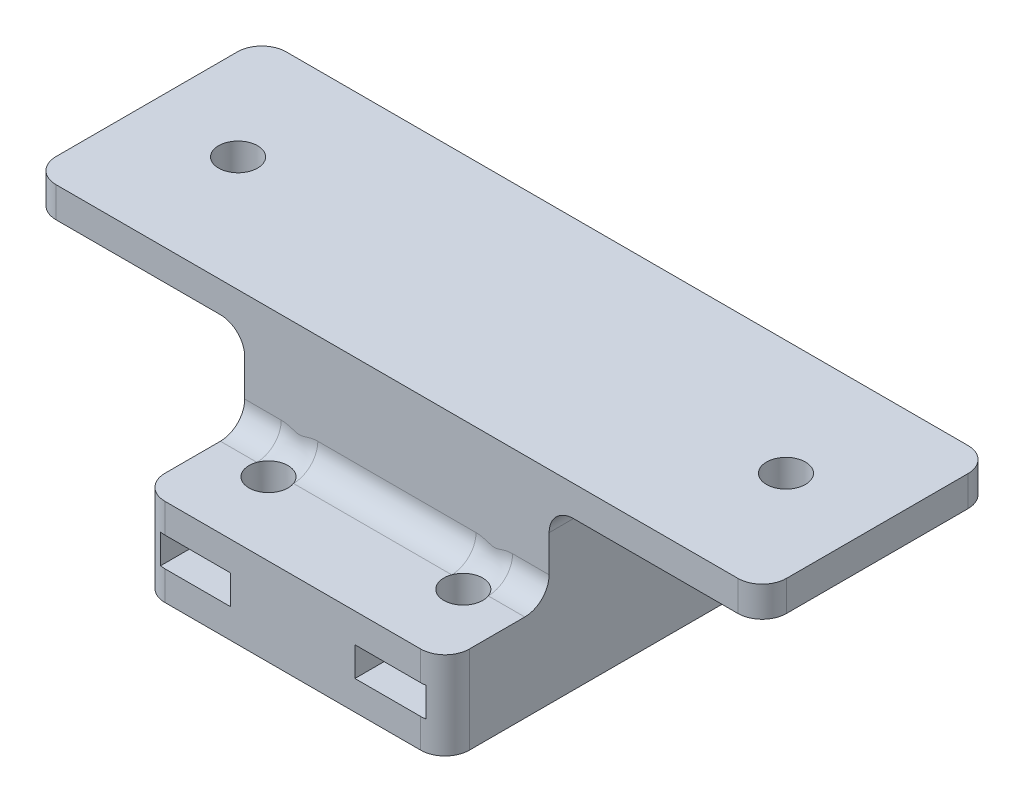
SolidWorks part; units mm, degrees
ref_plane "Front Plane" through (0, 0, 0) normal (0, 0, 1) x (1, 0, 0)
ref_plane "Top Plane" through (0, 0, 0) normal (0, 1, 0) x (1, 0, 0)
ref_plane "Right Plane" through (0, 0, 0) normal (1, 0, 0) x (0, 0, -1)
sketch "Sketch2" plane through (0, 0, 0) normal (0, 1, 0) x (1, 0, 0)
  line L1 (-12.5, 18) -> (12.5, 18)
  line L2 (-12.5, 18) -> (-12.5, -18)
  line L3 (-12.5, -18) -> (12.5, -18)
  line L4 (12.5, 18) -> (12.5, -18)
  line L5 (-12.5, 18) -> (12.5, -18) construction
  line L6 (-12.5, -18) -> (12.5, 18) construction
  point P0 (0, 0)
  dimension "D1" = 25
  dimension "D2" = 36
extrude "Boss-Extrude1" add sketch "Sketch2" along normal blind 7.2
fillet "Fillet1" radius 2 4 edges at (-12.5, 3.6, -18) (-12.5, 3.6, 18) (12.5, 3.6, -18) (12.5, 3.6, 18)
sketch "Sketch3" plane through (0, 0, 0) normal (0, -1, 0) x (1, 0, 0)
  line L1 (-8, 12) -> (8, 12)
  line L2 (-8, 12) -> (-8, -12)
  line L3 (-8, -12) -> (8, -12)
  line L4 (8, 12) -> (8, -12)
  line L5 (-8, 12) -> (8, -12) construction
  line L6 (-8, -12) -> (8, 12) construction
  circle A0 centre (-8, 12) radius 1.6
  circle A1 centre (8, 12) radius 1.6
  circle A2 centre (8, -12) radius 1.6
  circle A3 centre (-8, -12) radius 1.6
  point P0 (0, 0)
  dimension "D3" = 3.2
  dimension "D1" = 16
  dimension "D2" = 24
extrude "Cut-Extrude1" cut sketch "Sketch3" against normal up to surface (7.2 mm away) contours L4 A1 L1 | L2 A3 L3 | L3 A2 L4 | L4 A2 L3 | L3 A3 L2 | L1 A0 L2 | L2 A0 L1 | L1 A1 L4 | A1 region at (-8.2264, 0, 12.2264) region at (-7.3209, 0, 11.3209) region at (8.2264, 0, 12.2264) region at (7.3209, 0, 11.3209) region at (-7.3209, 0, -11.3209) region at (-8.2264, 0, -12.2264) region at (8.2264, 0, -12.2264) region at (7.3209, 0, -11.3209) up to face at (0, 7.2, 0)
sketch "Sketch4" plane through (0, 7.2, 0) normal (0, 1, 0) x (1, 0, 0)
  line L0 (8, -10.33) -> (8, -18) construction
  line L1 (-10.5, -18) -> (10.5, -18) construction
  line L2 (5.1, -10.33) -> (10.9, -10.33)
  line L3 (5.1, -10.33) -> (5.1, -18)
  line L4 (5.1, -18) -> (10.9, -18)
  line L5 (10.9, -10.33) -> (10.9, -18)
  line L6 (5.1, -10.33) -> (8, -8.65)
  line L7 (8, -8.65) -> (10.9, -10.33)
  circle M2 centre (8, -12) radius 1.6
  line M10 (-10.5, -18) -> (10.5, -18)
  arc M11 (10.5, -18) -> (12.5, -16) centre (10.5, -16) ccw
  dimension "D1" = 7.67
  dimension "D2" = 5.8
  dimension "D3" = 9.35
extrude "Cut-Extrude2" cut sketch "Sketch4" against normal blind 2.4 from offset 2.4 contours L0 L2 L3 M10 M2 | L2 L0 L4 L5 M2 M11 | L7 L6 L2 region at (9.6198, 7.2, 14.6418) region at (6.3799, 7.2, 14.6428) region at (8, 7.2, 9.77) offset against normal yes
mirror "Mirror1" about plane through (0, 0, 0) normal (1, 0, 0) of "Cut-Extrude2"
mirror "Mirror2" about plane through (0, 0, 0) normal (0, 0, 1) of "Mirror1"
sketch "Sketch5" plane through (0, 7.2, 0) normal (0, 1, 0) x (1, 0, 0)
  line L0 (12.5, -16) -> (12.5, 16) construction
  line L1 (-12.5, 9.45) -> (12.5, 9.45)
  line L2 (-12.5, 9.45) -> (-12.5, -9.45)
  line L3 (-12.5, -9.45) -> (12.5, -9.45)
  line L4 (12.5, 9.45) -> (12.5, -9.45)
  line L5 (-12.5, 9.45) -> (12.5, -9.45) construction
  line L6 (-12.5, -9.45) -> (12.5, 9.45) construction
  point P0 (0, 0)
  dimension "D1" = 18.9
extrude "Boss-Extrude2" add sketch "Sketch5" along normal blind 7
sketch "Sketch6" plane through (0, 14.2, 0) normal (0, 1, 0) x (1, 0, 0)
  line L0 (12.5, 9.45) -> (-12.5, 9.45) construction
  line L1 (-30, 9.45) -> (30, 9.45)
  line L2 (-30, 9.45) -> (-30, -9.45)
  line L3 (-30, -9.45) -> (30, -9.45)
  line L4 (30, 9.45) -> (30, -9.45)
  line L5 (-30, 9.45) -> (30, -9.45) construction
  line L6 (-30, -9.45) -> (30, 9.45) construction
  point P0 (0, 0)
  dimension "D1" = 60
extrude "Boss-Extrude3" add sketch "Sketch6" along normal blind 2.5
sketch "Sketch7" plane through (0, 16.7, 0) normal (0, 1, 0) x (1, 0, 0)
  line L0 (-22.5, 0) -> (22.5, 0) construction
  circle A0 centre (-22.5, 0) radius 1.6
  circle A1 centre (22.5, 0) radius 1.6
  dimension "D2" = 3.2
  dimension "D1" = 45
extrude "Cut-Extrude3" cut sketch "Sketch7" against normal through all
fillet "Fillet2" radius 2 4 edges at (-30, 15.45, -9.45) (30, 15.45, -9.45) (30, 15.45, 9.45) (-30, 15.45, 9.45)
fillet "Fillet3" radius 2 4 edges
